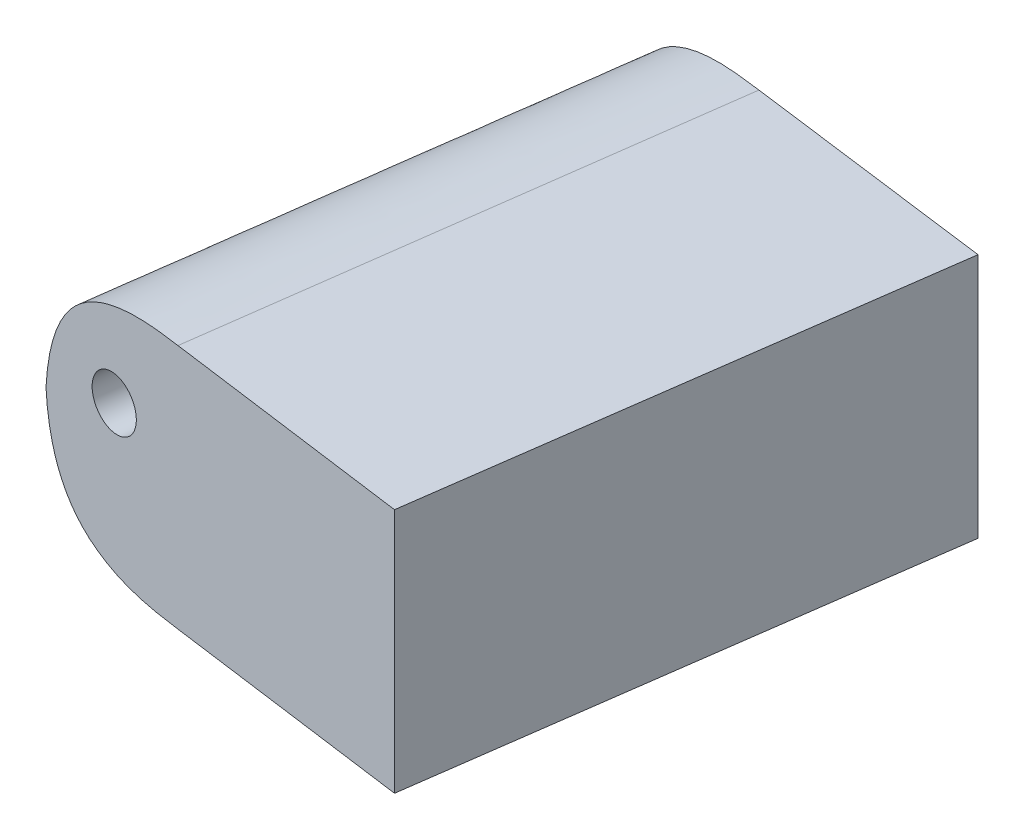
SolidWorks part; units mm, degrees
ref_plane "Front Plane" through (0, 0, 0) normal (0, 0, 1) x (1, 0, 0)
ref_plane "Top Plane" through (0, 0, 0) normal (0, 1, 0) x (1, 0, 0)
ref_plane "Right Plane" through (0, 0, 0) normal (1, 0, 0) x (0, 0, -1)
sketch "Sketch1" plane through (0, 0, 0) normal (0, 1, 0) x (1, 0, 0)
  line L12 (-29.6265, -8.5598) -> (-45.2825, -6.4414)
  line L13 (-26.8764, 11.317) -> (-29.6265, -8.5598)
  line L14 (-42.6007, 13.378) -> (-26.8764, 11.317)
  line L15 (-42.6007, 13.378) -> (-45.2825, -6.4414)
extrude "Boss-Extrude1" add sketch "Sketch1" along normal blind 9.525
sketch "Sketch3" plane through (1.0043, 0, -7.6627) normal (0.13, 0, -0.9915) x (-0.9915, 0, -0.13)
  line L0 (43.978, 9.525) -> (43.978, 5.969) construction
  line L2 (43.978, 9.525) -> (43.978, 0) construction
  line L3 (43.978, 5.969) -> (40.946, 5.969) construction
  circle A3 centre (40.946, 5.969) radius 2.032
extrude "Cut-Extrude1" cut sketch "Sketch3" against normal blind 2.7
sketch "Sketch4" plane through (0.6535, 0, -4.9856) normal (0.13, 0, -0.9915) x (-0.9915, 0, -0.13)
  circle A0 centre (40.946, 5.969) radius 1
extrude "Cut-Extrude2" cut sketch "Sketch4" against normal through all
fillet "Fillet2" radius 6 2 edges at (-43.9416, 9.525, -3.4683) (-43.9416, 0, -3.4683) curvature continuous yes
